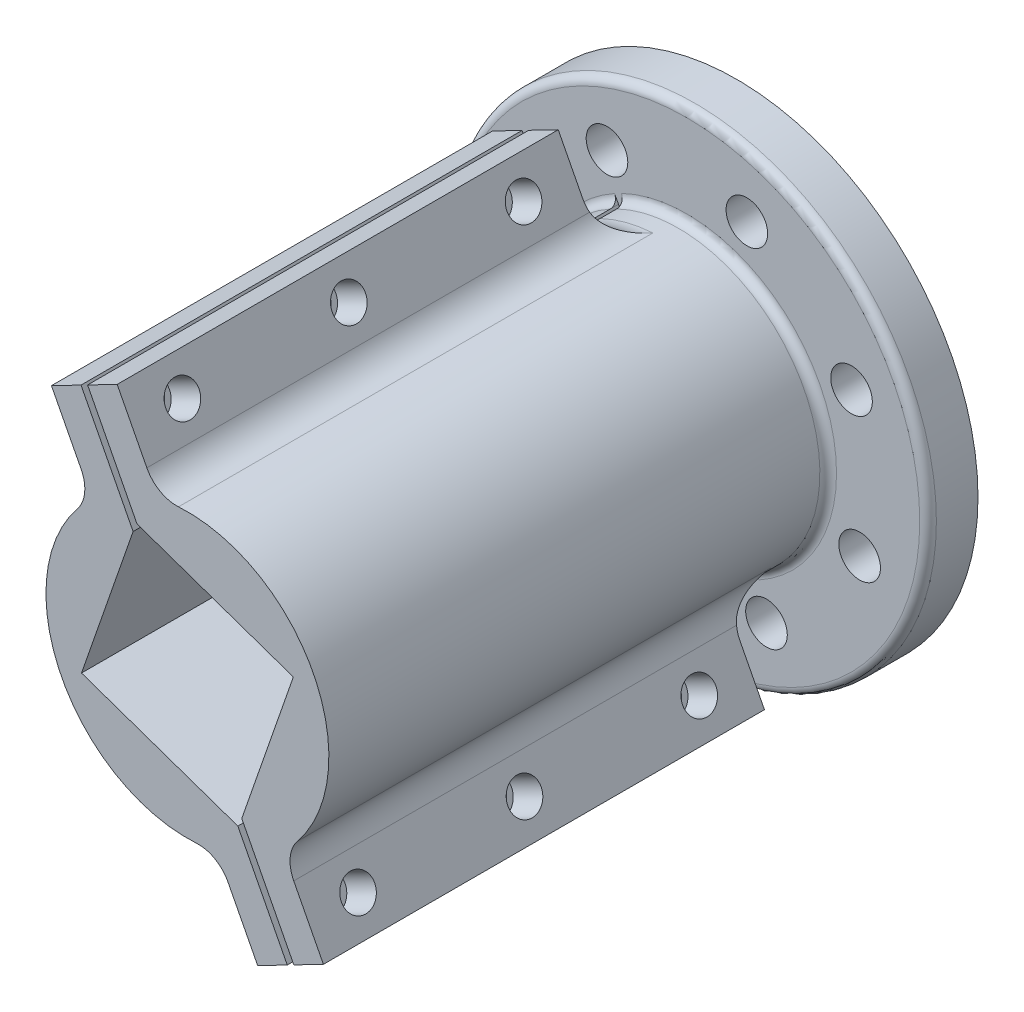
SolidWorks part; units mm, degrees
ref_plane "前视基准面" through (0, 0, 0) normal (0, 0, 1) x (1, 0, 0)
ref_plane "上视基准面" through (0, 0, 0) normal (0, 1, 0) x (1, 0, 0)
ref_plane "右视基准面" through (0, 0, 0) normal (1, 0, 0) x (0, 0, -1)
sketch "草图1" plane through (0, 0, 0) normal (0, 0, 1) x (1, 0, 0)
  line L0 (1.9417, -4.0121) -> (-2.8502, 5.8893) construction
  line L1 (1.9417, -4.0121) -> (5.5546, 6.3777) construction
  circle A0 centre (-2.8502, 5.8893) radius 1.25
  circle A1 centre (5.5546, 6.3777) radius 1.25
  circle A2 centre (11.8431, 0.7799) radius 1.25
  circle A3 centre (12.3314, -7.625) radius 1.25
  circle A4 centre (6.7336, -13.9134) radius 1.25
  circle A5 centre (-1.6712, -14.4018) radius 1.25
  circle A6 centre (-7.9597, -8.804) radius 1.25
  circle A7 centre (-8.448, -0.3991) radius 1.25
  circle A8 centre (1.9417, -4.0121) radius 14.5
  dimension "D1" = 2.5
  dimension "D3" = 29
  dimension "D2" = 45
extrude "凸台-拉伸1" add sketch "草图1" along normal blind 3
sketch "草图2" plane through (0, 0, 3) normal (0, 0, 1) x (1, 0, 0)
  line L0 (1.9417, -4.0121) -> (0.8179, 10.4443)
  line L1 (1.9417, -4.0121) -> (6.7336, -13.9134)
  line L2 (1.9417, -4.0121) -> (6.0399, -11.4588)
  line L3 (1.9417, -4.0121) -> (-1.7612, 3.639)
  line L4 (1.9417, -4.0121) -> (-2.1565, 3.4347)
  circle A0 centre (1.9417, -4.0121) radius 8.5
  circle A1 centre (1.9417, -4.0121) radius 14.5 construction
  circle A2 centre (1.9417, -4.0121) radius 6.5
  dimension "D2" = 17
  dimension "D3" = 13
  dimension "D1" = 0
  dimension "D4" = 3
  dimension "D5" = 180
  dimension "D6" = 180
extrude "凸台-拉伸2" add sketch "草图2" along normal blind 30 contours A2 L4 A0 L1 | A2 L2 A0 L0 | A2 L0 A0 L3
fillet "圆角2" radius 0.5 3 edges at (9.4932, -0.1102, 3) (-5.6098, -7.9139, 3) (16.4417, -4.0121, 3)
ref_plane "基准面4" through (5.9459, -11.5074, 0) normal (0.459, -0.8884, 0) x (-0.8884, -0.459, 0)
sketch "草图5" plane through (5.9459, -11.5074, 0) normal (0.459, -0.8884, 0) x (-0.8884, -0.459, 0)
  line L0 (0.3392, -3.5) -> (8.6167, -3.5) construction
  line L1 (0.3392, -33) -> (2.3392, -33)
  line L2 (0.3392, -33) -> (0.3392, -6.5)
  line L3 (0.3392, -6.5) -> (2.3392, -6.5)
  line L4 (2.3392, -33) -> (2.3392, -6.5)
  line L5 (-0.1058, -3.5) -> (-8.3833, -3.5) construction
  line L6 (-0.1058, -33) -> (-2.1058, -33)
  line L7 (-0.1058, -33) -> (-0.1058, -6.5)
  line L8 (-0.1058, -6.5) -> (-2.1058, -6.5)
  line L9 (-2.1058, -33) -> (-2.1058, -6.5)
  dimension "D1" = 3
  dimension "D2" = 3
  dimension "D3" = 2
  dimension "D4" = 2
extrude "凸台-拉伸4" add sketch "草图5" along normal blind 5 and the other way blind 1
fillet "圆角4" radius 2 2 edges at (3.7333, -12.3211, 19.75) (7.6823, -10.2806, 19.75)
fillet "圆角5" radius 2 2 edges at (4.1014, -12.2331, 6.5) (7.3976, -10.53, 6.5)
ref_plane "基准面5" through (-1.8552, 3.5904, 0) normal (-0.459, 0.8884, 0) x (0.8884, 0.459, 0)
sketch "草图6" plane through (-1.8552, 3.5904, 0) normal (-0.459, 0.8884, 0) x (0.8884, 0.459, 0)
  line L1 (-0.3392, -33) -> (-2.3392, -33)
  line L2 (-0.3392, -33) -> (-0.3392, -6.5)
  line L3 (-0.3392, -6.5) -> (-2.3392, -6.5)
  line L4 (-2.3392, -33) -> (-2.3392, -6.5)
  line L5 (0.1058, -33) -> (2.1058, -33)
  line L6 (0.1058, -33) -> (0.1058, -6.5)
  line L7 (0.1058, -6.5) -> (2.1058, -6.5)
  line L8 (2.1058, -33) -> (2.1058, -6.5)
  line L11 (0.1058, -3.5) -> (8.3833, -3.5) construction
  line L12 (-0.3392, -3.5) -> (-8.6167, -3.5) construction
  dimension "D1" = 2
  dimension "D2" = 2
  dimension "D3" = 3
  dimension "D4" = 3
extrude "凸台-拉伸5" add sketch "草图6" along normal blind 5 and the other way blind 1
fillet "圆角6" radius 2 4 edges at (-3.7989, 2.2565, 19.75) (0.1501, 4.297, 19.75) (-3.0129, 2.8946, 6.5) (-0.8252, 4.025, 6.5)
sketch "草图7" plane through (-2.0782, -1.0738, 0) normal (-0.8884, -0.459, 0) x (0, 0, 1)
  line L0 (6.5, 9.0414) -> (33, 9.0414) construction
  line L1 (33, 5.1579) -> (33, 9.0414) construction
  line L2 (6.5, 5.8064) -> (6.5, 9.0414) construction
  line L3 (33, -14.0692) -> (33, -17.9528) construction
  line L5 (33, -17.9528) -> (6.5, -17.9528) construction
  line L6 (6.5, -14.7178) -> (6.5, -17.9528) construction
  circle A0 centre (30, 7.0414) radius 1
  circle A1 centre (9.5, 7.0414) radius 1
  circle A2 centre (20, 7.0414) radius 1
  circle A3 centre (30, -15.9528) radius 1
  circle A4 centre (9.5, -15.9528) radius 1
  circle A5 centre (20, -15.9528) radius 1
  dimension "D2" = 2
  dimension "D4" = 2
  dimension "D7" = 2
  dimension "D9" = 2
  dimension "D12" = 2
  dimension "D15" = 2
  dimension "D1" = 2
  dimension "D3" = 3
  dimension "D5" = 2
  dimension "D6" = 3
  dimension "D8" = 10
  dimension "D10" = 3
  dimension "D11" = 2
  dimension "D13" = 2
  dimension "D14" = 3
  dimension "D16" = 10
extrude "切除-拉伸2" cut sketch "草图7" against normal blind 5
ref_plane "基准面6" through (5.0756, -9.7067, 33) normal (0.8761, 0.4821, 0) x (0, 0, -1)
ref_plane "基准面7" through (0, 0, 3) normal (0, 0, 1) x (1, 0, 0)
sketch "草图9" plane through (0, 0, 3) normal (0, 0, 1) x (1, 0, 0)
  circle A0 centre (1.9417, -4.0121) radius 7
  dimension "D1" = 14
extrude "切除-拉伸3" cut sketch "草图9" along normal blind 30
sketch "草图12" plane through (0, 0, 33) normal (0, 0, 1) x (1, 0, 0)
  line L5 (-4.4207, -7.3019) -> (4.9076, -10.1404)
  line L6 (5.4619, -10.0625) -> (8.3041, -0.7222)
  line L7 (8.3041, -0.7222) -> (-1.0242, 2.1163)
  line L8 (-1.5785, 2.0384) -> (-4.4207, -7.3019)
  line L10 (4.9911, -10.3129) -> (4.9076, -10.1404)
  line L11 (-1.1077, 2.2888) -> (-1.0242, 2.1163)
  arc A2 (-1.4333, 2.1206) -> (4.9911, -10.3129) centre (1.9417, -4.0121) ccw construction
  arc A3 (5.3167, -10.1447) -> (-1.1077, 2.2888) centre (1.9417, -4.0121) ccw construction
  arc A4 (-1.4333, 2.1206) -> (4.9911, -10.3129) centre (1.9417, -4.0121) ccw
  arc A5 (5.4619, -10.0625) -> (-1.1077, 2.2888) centre (1.9417, -4.0121) ccw
  arc M2 (4.9911, -10.3129) -> (-1.4333, 2.1206) centre (1.9417, -4.0121) cw
extrude "凸台-拉伸8" add sketch "草图12" against normal blind 32 contours L8 M2 | L7 A5 L11 | L6 A5 | L10 L5 M2
sketch "草图13" plane through (0, 0, 33) normal (0, 0, 1) x (1, 0, 0)
  line L0 (8.0844, -0.6554) -> (8.3041, -0.7222)
  line L1 (8.2354, -0.9479) -> (8.3041, -0.7222)
  line L2 (8.0844, -0.6554) -> (-1.0242, 2.1163) construction
  line L3 (5.4619, -10.0625) -> (8.2354, -0.9479) construction
  line L4 (8.0844, -0.6554) -> (8.2354, -0.9479)
  arc A0 (8.2354, -0.9479) -> (8.0844, -0.6554) centre (1.9417, -4.0121) ccw construction
  arc A1 (8.2354, -0.9479) -> (8.0844, -0.6554) centre (1.9417, -4.0121) ccw construction
  dimension "D1" = 180
  dimension "D2" = 180
extrude "切除-拉伸4" cut sketch "草图13" against normal blind 30
sketch "草图14" plane through (0, 0, 33) normal (0, 0, 1) x (1, 0, 0)
  line L0 (-1.5785, 2.0384) -> (-1.5147, 2.2686)
  line L1 (18.9657, -34.9461) -> (-8.8145, 15.5328) construction
  line L2 (-1.5785, 2.0384) -> (-1.4333, 2.1206)
  line L3 (-1.5147, 2.2686) -> (-1.4333, 2.1206)
  arc A0 (-1.4333, 2.1206) -> (-1.5785, 2.0384) centre (1.9417, -4.0121) ccw construction
  dimension "D1" = 45
extrude "切除-拉伸5" cut sketch "草图14" against normal blind 30 contours L3 L2 L0
sketch "草图15" plane through (0, 0, 33) normal (0, 0, 1) x (1, 0, 0)
  line L0 (-4.352, -7.0762) -> (-4.4207, -7.3019)
  line L1 (-4.4207, -7.3019) -> (-4.201, -7.3687)
  line L2 (-1.5785, 2.0384) -> (-4.352, -7.0762) construction
  line L3 (-4.201, -7.3687) -> (4.9076, -10.1404) construction
  line L4 (-4.352, -7.0762) -> (-4.201, -7.3687)
  dimension "D1" = 180
  dimension "D2" = 180
extrude "切除-拉伸6" cut sketch "草图15" against normal blind 30
sketch "草图16" plane through (0, 0, 33) normal (0, 0, 1) x (1, 0, 0)
  line L0 (5.4619, -10.0625) -> (5.3981, -10.2927)
  line L1 (18.9657, -34.9461) -> (-8.8145, 15.5328) construction
  line L2 (5.4619, -10.0625) -> (5.3167, -10.1447)
  line L3 (5.3167, -10.1447) -> (5.3981, -10.2927)
  arc A0 (5.3167, -10.1447) -> (5.4619, -10.0625) centre (1.9417, -4.0121) ccw construction
  arc A1 (5.3167, -10.1447) -> (5.4619, -10.0625) centre (1.9417, -4.0121) ccw construction
  dimension "D1" = 45
extrude "切除-拉伸7" cut sketch "草图16" against normal blind 30
sketch "草图17" plane through (0, 0, 33) normal (0, 0, 1) x (1, 0, 0)
  line L0 (-1.5147, 2.2686) -> (-4.4207, -7.3019)
  line L1 (-2.0647, 0.01) -> (-3.8637, -5.9148)
  line L2 (-3.8637, -5.9148) -> (-4.2963, -7.3397)
  line L3 (-1.5785, 2.0384) -> (-1.5147, 2.2686) construction
  line L4 (-1.5785, 2.0384) -> (-1.5147, 2.2686) construction
  line L5 (-4.4207, -7.3019) -> (-4.2963, -7.3397)
  line L6 (-4.4207, -7.3019) -> (4.9076, -10.1404) construction
  line L7 (-2.0647, 0.01) -> (-1.4272, 2.1095)
  line L8 (-1.5147, 2.2686) -> (-1.4272, 2.1095)
  line L9 (18.9657, -34.9461) -> (-8.8145, 15.5328) construction
  dimension "D1" = 0.13
  dimension "D2" = 180
  dimension "D3" = 180
extrude "凸台-拉伸9" add sketch "草图17" against normal blind 30
sketch "草图19" plane through (0, 0, 33) normal (0, 0, 1) x (1, 0, 0)
  line L0 (-1.4232, 2.1023) -> (-4.2963, -7.3397)
  line L1 (18.9657, -34.9461) -> (-8.8145, 15.5328) construction
  line L2 (-4.2963, -7.3397) -> (4.9076, -10.1404)
  line L3 (-1.4232, 2.1023) -> (-1.4272, 2.1095)
  line L4 (-4.2963, -7.3397) -> (-1.4272, 2.1095) construction
  line L5 (-1.4272, 2.1095) -> (-4.6964, -7.7435)
  line L6 (-4.6964, -7.7435) -> (4.9076, -10.1404)
  dimension "D1" = 90
extrude "凸台-拉伸11" add sketch "草图19" against normal blind 30
sketch "草图20" plane through (0, 0, 33) normal (0, 0, 1) x (1, 0, 0)
  line L0 (-1.0242, 2.1163) -> (8.3041, -0.7222)
  line L1 (8.3041, -0.7222) -> (5.3941, -10.2854)
  line L2 (18.9657, -34.9461) -> (-8.8145, 15.5328) construction
  line L3 (5.3981, -10.2927) -> (6.0399, -11.4588) construction
  line L4 (5.3941, -10.2854) -> (5.4317, -10.3537)
  line L5 (5.4317, -10.3537) -> (8.9463, -0.477)
  line L6 (8.9463, -0.477) -> (-1.0242, 2.1163)
  dimension "D1" = 90
extrude "凸台-拉伸12" add sketch "草图20" against normal blind 30
sketch "草图21" plane through (0, 0, 33) normal (0, 0, 1) x (1, 0, 0)
  line L7 (-7.9597, -8.804) -> (11.8431, 0.7799)
  line L8 (-2.8502, 5.8893) -> (6.7336, -13.9134)
  circle A0 centre (-2.8502, 5.8893) radius 1.25 construction
  circle A1 centre (6.7336, -13.9134) radius 1.25 construction
  circle A2 centre (11.8431, 0.7799) radius 1.25 construction
  circle A3 centre (-7.9597, -8.804) radius 1.25 construction
  circle A4 centre (-2.8502, 5.8893) radius 1.25
  circle A5 centre (6.7336, -13.9134) radius 1.25
  circle A6 centre (11.8431, 0.7799) radius 1.25
  circle A7 centre (-7.9597, -8.804) radius 1.25
  circle A8 centre (1.9417, -4.0121) radius 8
  line M9 (-1.0242, 2.1163) -> (8.3041, -0.7222)
  line M10 (8.3041, -0.7222) -> (5.3941, -10.2854)
  line M11 (5.3941, -10.2854) -> (6.0399, -11.4588)
extrude "凸台-拉伸13" add sketch "草图21" against normal blind 30 contours L8 L7 M9 M10 | L8 A8 L7 M11 M10 | L7 A8 L8 | L8 A8 L7
sketch "草图22" plane through (0, 0, 33) normal (0, 0, 1) x (1, 0, 0)
  line L0 (-2.8502, 5.8893) -> (6.7336, -13.9134)
  line L1 (11.8431, 0.7799) -> (-7.9597, -8.804)
  line L2 (-1.1382, 2.3518) -> (-4.4222, -7.092)
  line L3 (-4.4222, -7.092) -> (5.0216, -10.3759)
  line L4 (5.0216, -10.3759) -> (8.3056, -0.9322)
  line L5 (8.3056, -0.9322) -> (-1.1382, 2.3518)
  line L16 (-1.9154, 2.9967) -> (-2.1565, 3.4347)
  line L20 (4.3802, -13.5731) -> (6.1629, -17.0233)
  line L21 (6.1629, -17.0233) -> (7.9398, -16.1052)
  line L22 (7.9398, -16.1052) -> (5.6445, -11.6631)
  line L23 (5.6445, -11.6631) -> (5.4267, -11.2131)
  line L24 (5.7988, -11.0208) -> (6.0399, -11.4588)
  line L25 (6.0399, -11.4588) -> (8.3351, -15.9009)
  line L26 (8.3351, -15.9009) -> (10.1119, -14.9828)
  line L27 (10.1119, -14.9828) -> (8.3292, -11.5326)
  line L31 (-1.7612, 3.639) -> (-1.5433, 3.189)
  line L32 (-1.9154, 2.9967) -> (-2.1565, 3.4347)
  line L36 (4.3802, -13.5731) -> (6.1629, -17.0233)
  line L37 (6.1629, -17.0233) -> (7.9398, -16.1052)
  line L38 (7.9398, -16.1052) -> (5.6445, -11.6631)
  line L39 (5.6445, -11.6631) -> (5.4267, -11.2131)
  line L40 (5.7988, -11.0208) -> (6.0399, -11.4588)
  line L41 (6.0399, -11.4588) -> (8.3351, -15.9009)
  line L42 (8.3351, -15.9009) -> (10.1119, -14.9828)
  line L43 (10.1119, -14.9828) -> (8.3292, -11.5326)
  line L47 (-1.7612, 3.639) -> (-1.5433, 3.189)
  line L48 (-2.1565, 3.4347) -> (-4.4517, 7.8768)
  line L49 (-2.1565, 3.4347) -> (-4.4517, 7.8768)
  line L50 (-4.4517, 7.8768) -> (-6.2286, 6.9587)
  line L51 (-4.4517, 7.8768) -> (-6.2286, 6.9587)
  line L52 (-6.2286, 6.9587) -> (-4.4458, 3.5085)
  line L53 (-6.2286, 6.9587) -> (-4.4458, 3.5085)
  line L54 (-0.4968, 5.549) -> (-2.2795, 8.9992)
  line L55 (-0.4968, 5.549) -> (-2.2795, 8.9992)
  line L56 (-2.2795, 8.9992) -> (-4.0564, 8.0811)
  line L57 (-2.2795, 8.9992) -> (-4.0564, 8.0811)
  line L58 (-4.0564, 8.0811) -> (-1.7612, 3.639)
  line L59 (-4.0564, 8.0811) -> (-1.7612, 3.639)
  circle A0 centre (11.8431, 0.7799) radius 1.25 construction
  circle A1 centre (11.8431, 0.7799) radius 1.25
  circle A2 centre (-2.8502, 5.8893) radius 1.25 construction
  circle A3 centre (6.7336, -13.9134) radius 1.25 construction
  circle A4 centre (-7.9597, -8.804) radius 1.25 construction
  circle A5 centre (-2.8502, 5.8893) radius 1.25
  circle A6 centre (6.7336, -13.9134) radius 1.25
  circle A7 centre (-7.9597, -8.804) radius 1.25
  arc A8 (-1.5433, 3.189) -> (-1.9154, 2.9967) centre (1.9417, -4.0121) ccw
  arc A10 (-4.6676, 1.3328) -> (2.4774, -12.4952) centre (1.9417, -4.0121) ccw
  arc A11 (4.3802, -13.5731) -> (2.4774, -12.4952) centre (2.6034, -14.4912) ccw
  arc A12 (5.4267, -11.2131) -> (5.7988, -11.0208) centre (1.9417, -4.0121) ccw
  arc A13 (8.5509, -9.3569) -> (8.3292, -11.5326) centre (10.1061, -10.6146) ccw
  arc A14 (8.5509, -9.3569) -> (1.406, 4.4711) centre (1.9417, -4.0121) ccw
  arc A16 (-1.5433, 3.189) -> (-1.9154, 2.9967) centre (1.9417, -4.0121) ccw
  arc A18 (-4.6676, 1.3328) -> (2.4774, -12.4952) centre (1.9417, -4.0121) ccw
  arc A19 (4.3802, -13.5731) -> (2.4774, -12.4952) centre (2.6034, -14.4912) ccw
  arc A20 (5.4267, -11.2131) -> (5.7988, -11.0208) centre (1.9417, -4.0121) ccw
  arc A21 (8.5509, -9.3569) -> (8.3292, -11.5326) centre (10.1061, -10.6146) ccw
  arc A22 (8.5509, -9.3569) -> (1.406, 4.4711) centre (1.9417, -4.0121) ccw
  circle A24 centre (1.9417, -4.0121) radius 7.07
  arc A31 (-4.6676, 1.3328) -> (-4.4458, 3.5085) centre (-6.2227, 2.5905) ccw
  arc A32 (-4.6676, 1.3328) -> (-4.4458, 3.5085) centre (-6.2227, 2.5905) ccw
  arc A33 (-0.4968, 5.549) -> (1.406, 4.4711) centre (1.28, 6.4671) ccw
  arc A34 (-0.4968, 5.549) -> (1.406, 4.4711) centre (1.28, 6.4671) ccw
  dimension "D1" = 0
extrude "切除-拉伸8" cut sketch "草图22" against normal blind 30 contours L1 L5 L0 | L0 L4 L1 | L1 L3 L0 | L0 L2 L1
sketch "草图24" plane through (0, 0, 33) normal (0, 0, 1) x (1, 0, 0)
  line L0 (8.3351, -15.9009) -> (-4.0564, 8.0811)
  line L1 (-4.0564, 8.0811) -> (-4.4517, 7.8768)
  line L2 (-4.4517, 7.8768) -> (7.9398, -16.1052)
  line L3 (7.9398, -16.1052) -> (8.3351, -15.9009)
extrude "切除-拉伸15" cut sketch "草图24" against normal blind 30
